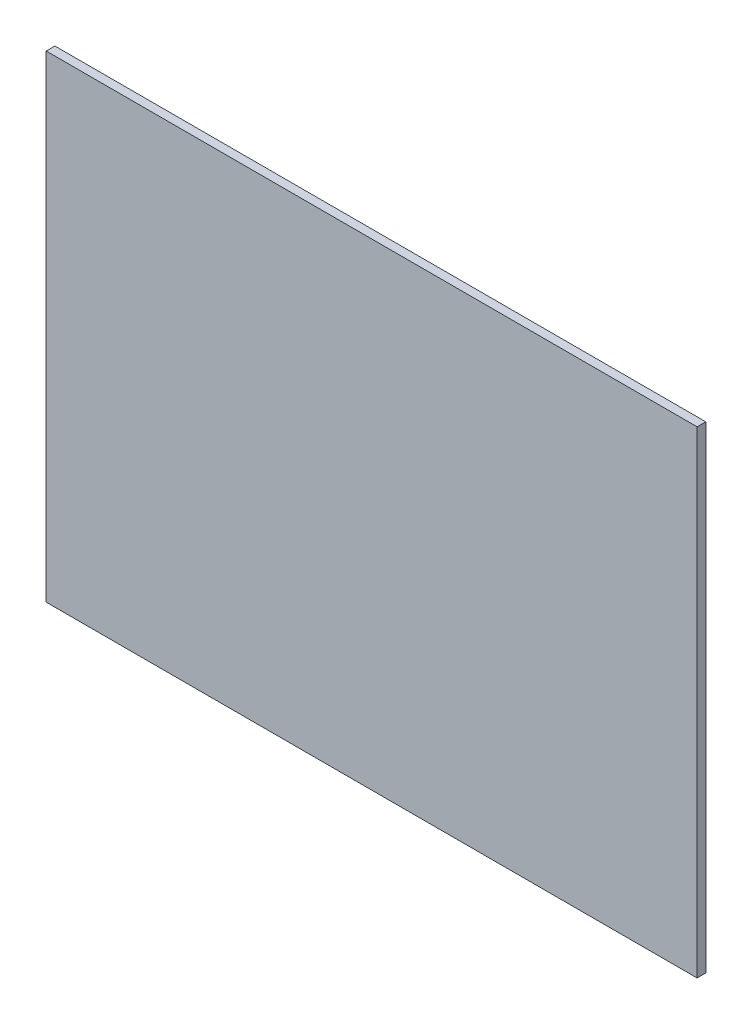
SolidWorks part; units mm, degrees
material "PC High Viscosity"
ref_plane "Front Plane" through (0, 0, 0) normal (0, 0, 1) x (1, 0, 0)
ref_plane "Top Plane" through (0, 0, 0) normal (0, 1, 0) x (1, 0, 0)
ref_plane "Right Plane" through (0, 0, 0) normal (1, 0, 0) x (0, 0, -1)
sketch "Sketch1" plane through (0, 0, 0) normal (0, 0, 1) x (1, 0, 0)
  line L1 (0, 0) -> (381, 0)
  line L2 (0, 0) -> (0, 279.4)
  line L3 (0, 279.4) -> (381, 279.4)
  line L4 (381, 0) -> (381, 279.4)
  dimension "D1" = 381
  dimension "D2" = 279.4
extrude "Boss-Extrude1" add sketch "Sketch1" along normal blind 5.08
